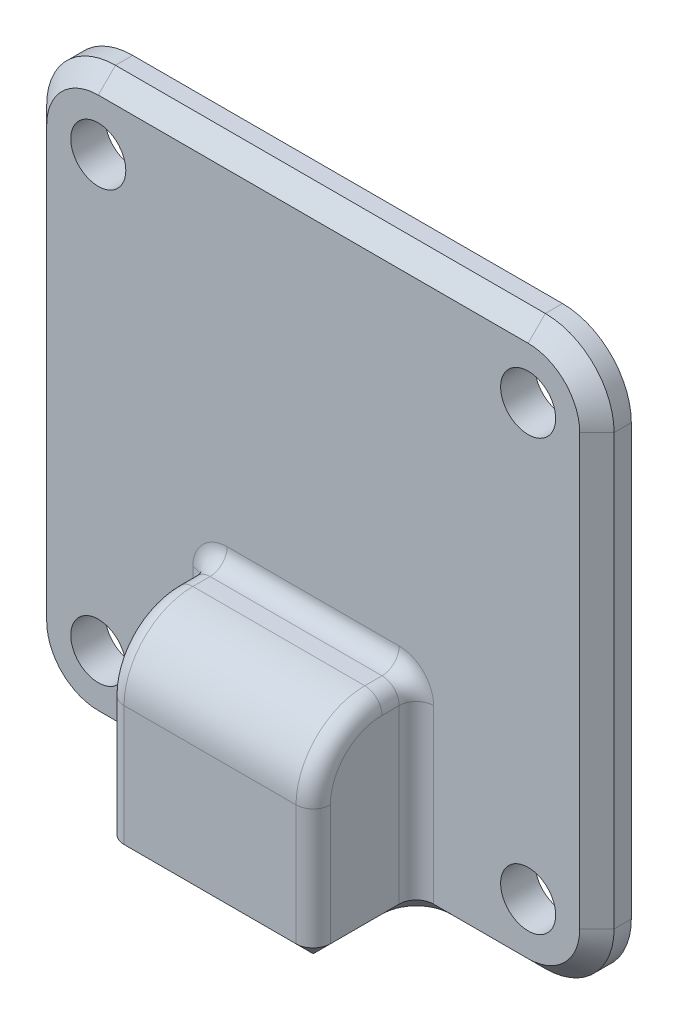
SolidWorks part; units mm, degrees
ref_plane "Front Plane" through (0, 0, 0) normal (0, 0, 1) x (1, 0, 0)
ref_plane "Top Plane" through (0, 0, 0) normal (0, 1, 0) x (1, 0, 0)
ref_plane "Right Plane" through (0, 0, 0) normal (1, 0, 0) x (0, 0, -1)
ref_axis "X" through (-88.99, 0, 0) along (1, 0, 0)
ref_axis "Y" through (0, 55, 0) along (0, -1, 0)
ref_axis "Z" through (0, 0, -88.99) along (0, 0, 1)
sketch "Sketch1" plane through (0, 0, 0) normal (0, 0, 1) x (1, 0, 0)
  line L20 (-16.5, -16.5) -> (16.5, -16.5)
  line L21 (-16.5, 16.5) -> (-16.5, -16.5)
  line L22 (16.5, 16.5) -> (-16.5, 16.5)
  line L23 (16.5, -16.5) -> (16.5, 16.5)
  line L24 (-12.5, -16.5) -> (12.5, -16.5)
  line L25 (-16.5, 12.5) -> (-16.5, -12.5)
  line L26 (12.5, 16.5) -> (-12.5, 16.5)
  line L27 (16.5, -12.5) -> (16.5, 12.5)
  circle A0 centre (-12.5, -12.5) radius 1.6 construction
  circle A1 centre (12.5, -12.5) radius 1.6 construction
  circle A2 centre (12.5, 12.5) radius 1.6 construction
  circle A3 centre (-12.5, 12.5) radius 1.6 construction
  circle A4 centre (-12.5, -12.5) radius 1.6
  circle A5 centre (12.5, -12.5) radius 1.6
  circle A6 centre (12.5, 12.5) radius 1.6
  circle A7 centre (-12.5, 12.5) radius 1.6
  arc A16 (-12.5, 16.5) -> (-16.5, 12.5) centre (-12.5, 12.5) ccw
  arc A17 (-12.5, -16.5) -> (-16.5, -12.5) centre (-12.5, -12.5) cw
  arc A18 (12.5, -16.5) -> (16.5, -12.5) centre (12.5, -12.5) ccw
  arc A19 (16.5, 12.5) -> (12.5, 16.5) centre (12.5, 12.5) ccw
  dimension "D2" = 4
  dimension "D1" = 4
extrude "Boss-Extrude1" add sketch "Sketch1" along normal blind 2
sketch "Sketch2" plane through (0, 0, 2) normal (0, 0, 1) x (1, 0, 0)
  line L0 (-6, -16.5) -> (-6, -4.5)
  line L1 (-12.5, -16.5) -> (12.5, -16.5) construction
  line L2 (-6, -4.5) -> (6, -4.5)
  line L3 (6, -4.5) -> (6, -16.5)
  line L4 (6, -16.5) -> (-6, -16.5)
  line L5 (0, -4.5) -> (0, 0) construction
  line L6 (-4, -16.5) -> (-4, -6.5)
  line L7 (-4, -6.5) -> (4, -6.5)
  line L8 (4, -6.5) -> (4, -16.5)
  point P9 (5.733, -6.8485)
  dimension "D1" = 12
  dimension "D2" = 12
  dimension "D3" = 2
extrude "Boss-Extrude2" add sketch "Sketch2" along normal blind 6 contours L0 L2 L3 L4
extrude "Cut-Extrude1" cut sketch "Sketch2<3>" along normal offset from surface 2 and the other way through all contours L8 L7 L6 L4 region at (0, -11.5, 2) up to face at (0, -10.5, 8)
sketch "Sketch2<3>" plane through (0, 0, 2) normal (0, 0, 1) x (1, 0, 0) same geometry as "Sketch2"
fillet "Fillet1" radius 4 1 edges at (0, -4.5, 8)
fillet "Fillet3" radius 1 9 edges at (-6, -10.5, 2) (6, -10.5, 2) (-6, -12.5, 8) (-6, -5.6716, 6.8284) (6, -12.5, 8) (6, -5.6716, 6.8284) (-6, -4.5, 3) (6, -4.5, 3) (0, -4.5, 2)
chamfer "Chamfer1" distance 1 angle 45 16 edges at (-9.75, -16.5, 2) (-15.3284, -15.3284, 2) (-16.5, 0, 2) (-15.3284, 15.3284, 2) (9.75, -16.5, 2) (0, 16.5, 2) (15.3284, -15.3284, 2) (15.3284, 15.3284, 2) (16.5, 0, 2) (-6, -16.5, 5) (6, -16.5, 5) (-6.2929, -16.5, 2.2929) (6.2929, -16.5, 2.2929) (-5.7071, -16.5, 7.7071) (0, -16.5, 8) (5.7071, -16.5, 7.7071)
